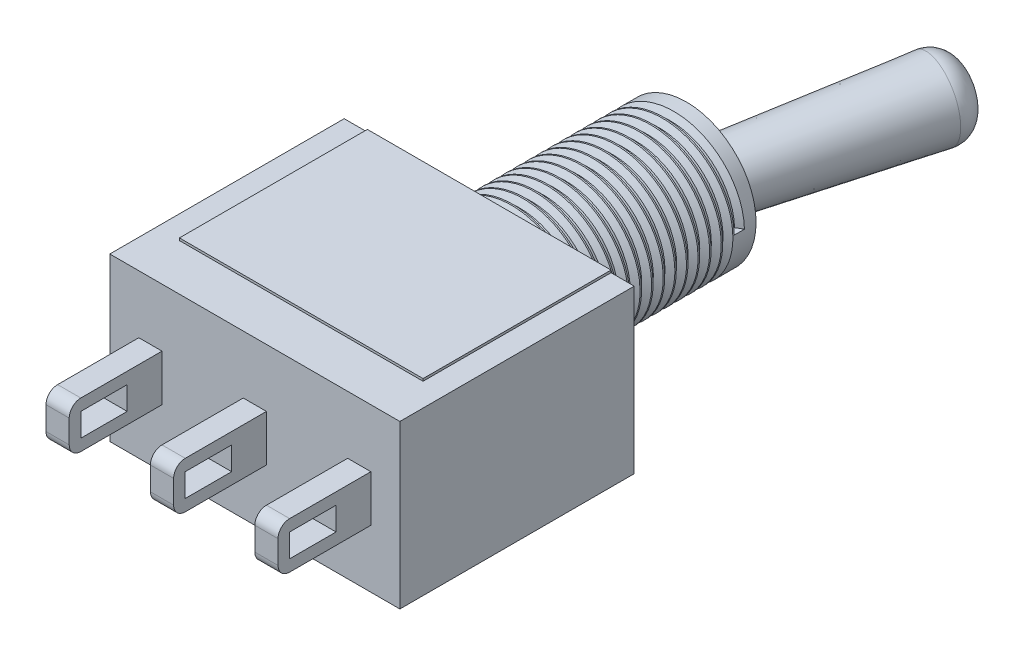
SolidWorks part; units mm, degrees
ref_plane "Front Plane" through (0, 0, 0) normal (0, 0, 1) x (1, 0, 0)
ref_plane "Top Plane" through (0, 0, 0) normal (0, 1, 0) x (1, 0, 0)
ref_plane "Right Plane" through (0, 0, 0) normal (1, 0, 0) x (0, 0, -1)
sketch "Sketch1" plane through (0, 0, 0) normal (0, 0, 1) x (1, 0, 0)
  line L1 (6.25, 3.5) -> (-6.25, 3.5)
  line L2 (6.25, 3.5) -> (6.25, -3.5)
  line L3 (6.25, -3.5) -> (-6.25, -3.5)
  line L4 (-6.25, 3.5) -> (-6.25, -3.5)
  line L5 (0, -3.5) -> (0, 3.5) construction
  line L6 (6.25, 0) -> (-6.25, 0) construction
  point P0 (0, 0)
  dimension "D1" = 12.5
  dimension "D2" = 7
extrude "Boss-Extrude1" add sketch "Sketch1" along normal blind 10
sketch "Sketch2" plane through (0, 0, 10) normal (0, 0, 1) x (1, 0, 0)
  line L0 (-5, 1) -> (-5, -1)
  line L1 (-5, 1) -> (-4, 1)
  line L2 (-5, -1) -> (-4, -1)
  line L3 (-4, 1) -> (-4, -1)
  line L4 (-0.5, 1) -> (-0.5, -1)
  line L5 (-0.5, 1) -> (0.5, 1)
  line L6 (-0.5, -1) -> (0.5, -1)
  line L7 (0.5, 1) -> (0.5, -1)
  line L8 (4, 1) -> (4, -1)
  line L9 (4, 1) -> (5, 1)
  line L10 (4, -1) -> (5, -1)
  line L11 (5, 1) -> (5, -1)
  point P0 (0, 1)
  point P11 (-0.5, 0)
  point P14 (4.5, 1)
  point P16 (-4.5, 1)
  dimension "D1" = 1
  dimension "D2" = 2
  dimension "D3" = 4.5
  dimension "D4" = 4.5
extrude "Boss-Extrude2" add sketch "Sketch2" along normal blind 4
sketch "Sketch3" plane through (-5, 0, 0) normal (-1, 0, 0) x (0, 0, 1)
  line L0 (14, 1) -> (14, -1) construction
  line L1 (13.5, 0.5) -> (11.5, 0.5)
  line L2 (13.5, 0.5) -> (13.5, -0.5)
  line L3 (13.5, -0.5) -> (11.5, -0.5)
  line L4 (11.5, 0.5) -> (11.5, -0.5)
  line L5 (12.5, -0.5) -> (12.5, 0.5) construction
  line L6 (13.5, 0) -> (11.5, 0) construction
  point P0 (12.5, 0)
  dimension "D1" = 0.5
  dimension "D2" = 2
  dimension "D3" = 1
extrude "Cut-Extrude1" cut sketch "Sketch3" against normal through all
sketch "Sketch14" plane through (0, 0, 0) normal (0, 0, -1) x (-1, 0, 0)
  line L0 (-6.25, -3.5) -> (6.25, -3.5)
  line L1 (-6.25, -3.5) -> (-6.25, 3.5)
  line L2 (6.25, -3.5) -> (6.25, 3.5)
  line L3 (-6.25, 3.5) -> (6.25, 3.5)
  line L4 (-6.25, 3.5) -> (6.25, 3.5) construction
extrude "Boss-Extrude9" add sketch "Sketch14" along normal blind 0.1
sketch "Sketch15" plane through (0, 3.5, 0) normal (0, 1, 0) x (1, 0, 0)
  line L0 (-5.25, 0.1) -> (-5.25, -8)
  line L1 (-5.25, 0.1) -> (5.25, 0.1)
  line L2 (-5.25, -8) -> (5.25, -8)
  line L3 (5.25, 0.1) -> (5.25, -8)
  line L4 (-6.25, 0.1) -> (6.25, 0.1) construction
  line L5 (-6.25, -10) -> (-6.25, 0.1) construction
  line L6 (6.25, -10) -> (6.25, 0.1) construction
  line L7 (6.25, -10) -> (-6.25, -10) construction
  dimension "D1" = 1
  dimension "D2" = 1
  dimension "D3" = 2
extrude "Boss-Extrude10" add sketch "Sketch15" along normal blind 0.1
sketch "Sketch16" plane through (0, -3.5, 0) normal (0, -1, 0) x (-1, 0, 0)
  line L0 (-5.25, 0.1) -> (-5.25, -8)
  line L1 (-5.25, 0.1) -> (5.25, 0.1)
  line L2 (-5.25, -8) -> (5.25, -8)
  line L3 (5.25, 0.1) -> (5.25, -8)
  line L4 (-6.25, 0.1) -> (6.25, 0.1) construction
  line L5 (6.25, -10) -> (-6.25, -10) construction
  line L6 (-6.25, -10) -> (-6.25, 0.1) construction
  line L7 (6.25, -10) -> (6.25, 0.1) construction
  dimension "D1" = 2
  dimension "D2" = 1
  dimension "D3" = 1
extrude "Boss-Extrude11" add sketch "Sketch16" along normal blind 0.1
fillet "Fillet1" radius 0.5 6 edges at (4.5, 1, 14) (4.5, -1, 14) (0, 1, 14) (0, -1, 14) (-4.5, 1, 14) (-4.5, -1, 14)
sketch "Sketch4" plane through (0, 0, -0.1) normal (0, 0, -1) x (-1, 0, 0)
  circle A0 centre (0, 0) radius 3
  dimension "D1" = 6
extrude "Boss-Extrude3" add sketch "Sketch4" along normal blind 8.5
sketch "Sketch5" plane through (0, 0, -8.6) normal (0, 0, -1) x (-1, 0, 0)
  circle A0 centre (0, 0) radius 2.5
  circle A1 centre (0, 0) radius 3 construction
  dimension "D1" = 0.5
extrude "Cut-Extrude2" cut sketch "Sketch5" against normal blind 1.5
thread "Thread1" pitch 0.5 method cut profile "Thread Profile1" start angle 0, offset 0.5, length 10, pitch 0.5, diameter 6
ref_plane "Plane1" through (3, 0, -8.1) normal (0, -1, 0) x (1, 0, 0)
sketch "Thread Profile1" plane through (3, 0, -8.1) normal (0, -1, 0) x (1, 0, 0)
  line L0 (0, 0) -> (0, 0.5) construction
  line L11 (0, 0) -> (0, 0.4375)
  line L12 (0, 0.4375) -> (-0.2706, 0.2812)
  line L13 (-0.2706, 0.2812) -> (-0.2706, 0.1562)
  line L15 (-0.2706, 0.1562) -> (0, 0)
  line L17 (-0.2706, 0.2187) -> (0, 0.2187) construction
  point P2 (0, 0)
  dimension "Pitch" = 0.5
  dimension "Profile_Angle" = 60
  dimension "Profile_Land" = 0.125
  dimension "Profile_Height" = 0.2706
sketch "Sketch9" plane through (0, 0, -7.1) normal (0, 0, -1) x (-1, 0, 0)
  line L0 (0, 0) -> (-0.2929, -2.246) construction
ref_plane "Plane3" through (1.7601, 0.2295, -6.6244) normal (0.2566, 0.0335, -0.9659) x (0.1293, -0.9916, 0)
sketch "Sketch10" plane through (1.7601, 0.2295, -6.6244) normal (0.2566, 0.0335, -0.9659) x (0.1293, -0.9916, 0)
  circle A0 centre (0, 1.8376) radius 1.25
  dimension "D1" = 2.5
extrude "Boss-Extrude5" add sketch "Sketch10" along normal blind 11 draft 2 draft outward yes
fillet "Fillet2" radius 1 1 edges at (1.2438, 0.3682, -18.1448)
sketch "Esquisse1" plane through (0, 0, -0.1) normal (0, 0, -1) x (-1, 0, 0)
  line L1 (-6.25, -6) -> (6.25, -6)
  line L2 (-6.25, -6) -> (-6.25, 6)
  line L3 (-6.25, 6) -> (6.25, 6)
  line L4 (6.25, -6) -> (6.25, 6)
  line L5 (-6.25, -6) -> (6.25, 6) construction
  line L6 (-6.25, 6) -> (6.25, -6) construction
  point P0 (0, 0)
  dimension "D1" = 12
